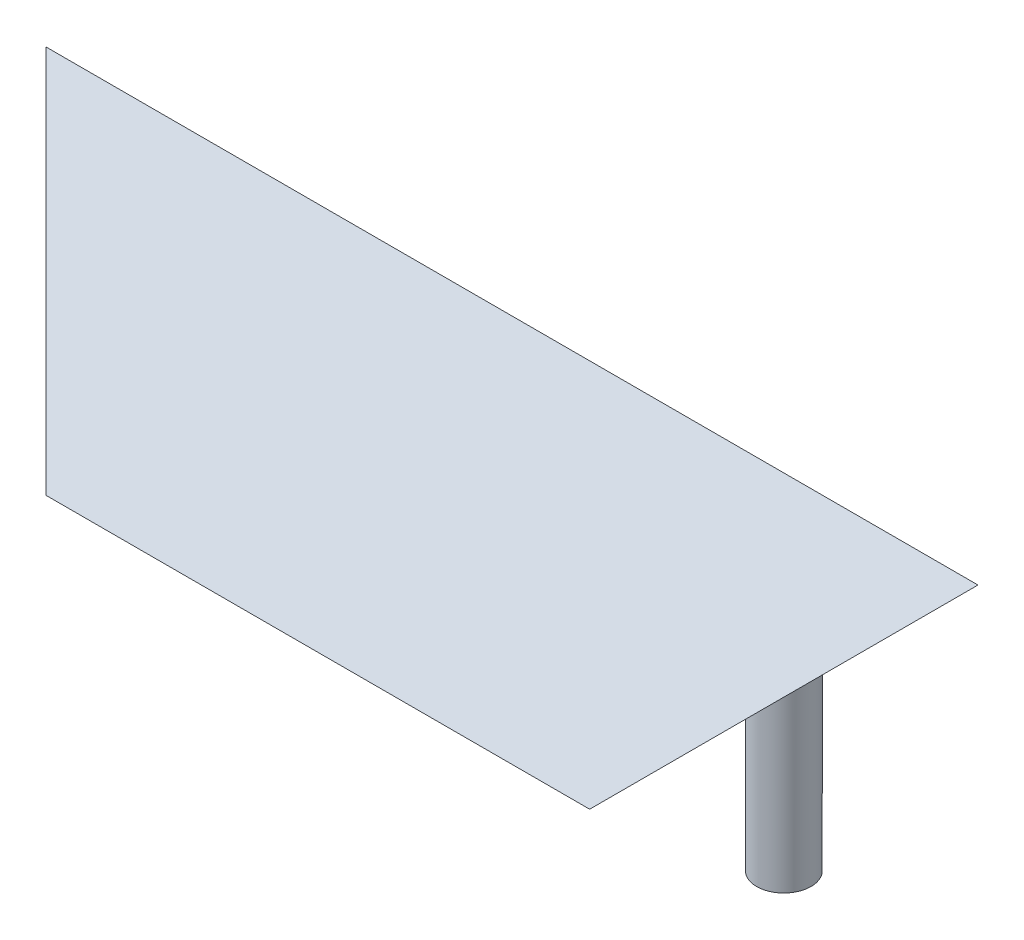
SolidWorks part; units mm, degrees
ref_plane "Front Plane" through (0, 0, 0) normal (0, 0, 1) x (1, 0, 0)
ref_plane "Top Plane" through (0, 0, 0) normal (0, 1, 0) x (1, 0, 0)
ref_plane "Right Plane" through (0, 0, 0) normal (1, 0, 0) x (0, 0, -1)
sketch "Sketch1" plane through (0, 0, 0) normal (0, 0, 1) x (1, 0, 0)
  line L0 (0, 0) -> (28, 0)
  line L1 (28, 0) -> (38, 10)
  line L2 (38, 10) -> (-10, 10)
  line L3 (-10, 10) -> (0, 0)
  dimension "D1" = 28
  dimension "D2" = 48
  dimension "D3" = 10
extrude "Boss-Extrude1" add sketch "Sketch1" along normal blind 10
chamfer "Chamfer1" distance 10 angle 45 1 edges at (14, 10, 10)
sketch "Sketch2" plane through (0, 0, 0) normal (0, -1, 0) x (1, 0, 0)
  line L0 (28, 10) -> (28, 0) construction
  line L1 (28, 0) -> (38, 0) construction
  line L2 (14, 0) -> (14, 10) construction
  line L3 (0, 0) -> (28, 0) construction
  line L4 (0, 10) -> (28, 10) construction
  circle A1 centre (31, 3) radius 1.4
  circle A3 centre (-3, 3) radius 1.4
  dimension "D1" = 3
  dimension "D2" = 3
extrude "Boss-Extrude2" add sketch "Sketch2" along normal blind 4.75 and the other way through all
sketch "Sketch4" plane through (0, 5, 5) normal (0, 0.7071, 0.7071) x (1, 0, 0)
  line L0 (-10, 7.0711) -> (0, -7.0711)
  line L1 (0, -7.0711) -> (28, -7.0711)
  line L2 (28, -7.0711) -> (38, 7.0711)
  line L3 (38, 7.0711) -> (-10, 7.0711)
extrude "Cut-Extrude1" cut sketch "Sketch4" along normal blind 5
